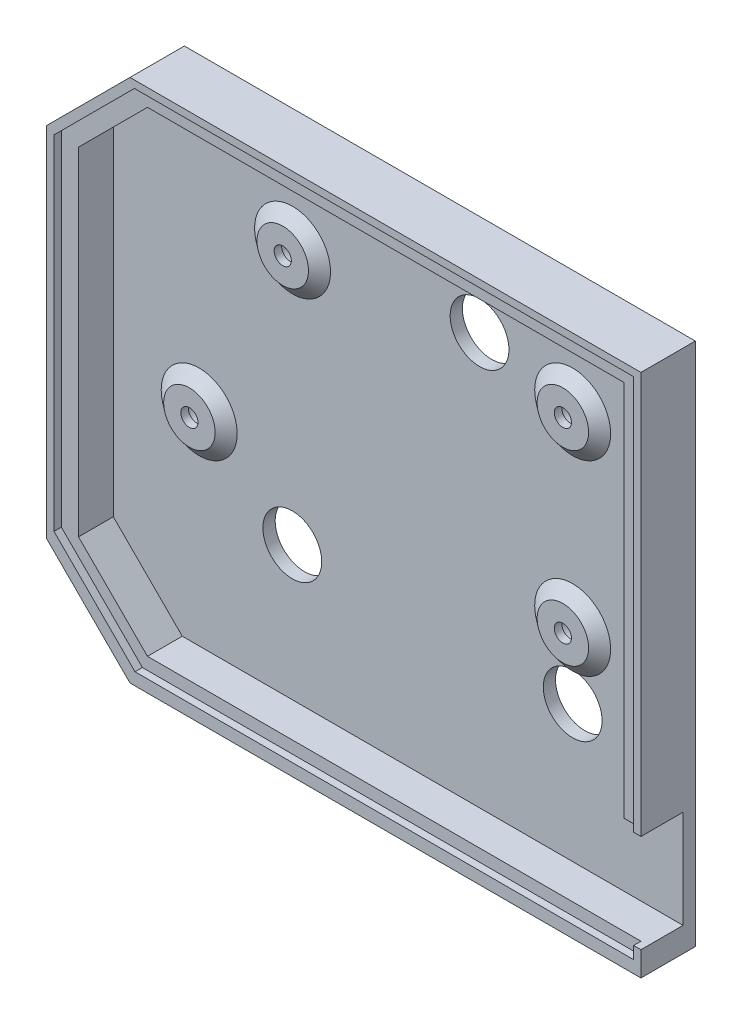
SolidWorks part; units mm, degrees
ref_plane "Plan de face" through (0, 0, 0) normal (0, 0, 1) x (1, 0, 0)
ref_plane "Plan de dessus" through (0, 0, 0) normal (0, 1, 0) x (1, 0, 0)
ref_plane "Plan de droite" through (0, 0, 0) normal (1, 0, 0) x (0, 0, -1)
sketch "Esquisse1" plane through (0, 0, 0) normal (0, 0, 1) x (1, 0, 0)
  line L0 (0, -85) -> (17, -102)
  line L4 (121.25, 5) -> (121.25, -102)
  line L5 (17, 5) -> (0, -12)
  line L7 (121.25, 5) -> (17, 5)
  line L8 (0, -12) -> (0, -85)
  line L9 (17, -102) -> (121.25, -102)
  dimension "D1" = 107
  dimension "D2" = 121.25
  dimension "D3" = 17
  dimension "D4" = 17
  dimension "D5" = 17
  dimension "D6" = 17
extrude "Boss.-Extru.1" add sketch "Esquisse1" along normal blind 2.5
sketch "Esquisse2" plane through (0, 0, 2.5) normal (0, 0, 1) x (1, 0, 0)
  line L0 (0, -12) -> (0, -85) construction
  line L1 (5, 0) -> (116.25, 0) construction
  line L2 (5, 0) -> (5, -97) construction
  line L3 (5, -97) -> (116.25, -97) construction
  line L4 (116.25, 0) -> (116.25, -97) construction
  line L5 (17, -102) -> (121.25, -102) construction
  line L6 (121.25, -102) -> (121.25, 5) construction
  line L7 (121.25, 5) -> (17, 5) construction
  line L9 (5, -82.9289) -> (19.0711, -97)
  line L10 (0, -85) -> (17, -102) construction
  line L11 (5, -14.0711) -> (19.0711, 0)
  line L12 (17, 5) -> (0, -12) construction
  line L13 (116.25, 0) -> (19.0711, 0)
  line L14 (5, -14.0711) -> (5, -82.9289)
  line L15 (19.0711, -97) -> (116.25, -97)
  line L16 (121.25, 5) -> (121.25, -102) construction
  line L17 (121.25, -102) -> (17, -102)
  line L18 (17, -102) -> (0, -85)
  line L19 (0, -85) -> (0, -12)
  line L20 (0, -12) -> (17, 5)
  line L21 (17, 5) -> (121.25, 5)
  line L30 (121.25, -2.5) -> (121.25, 5)
  line L31 (116.25, -97) -> (121.25, -97)
  line L32 (121.25, -97) -> (121.25, -102)
  line L33 (116.25, 0) -> (116.25, -77)
  line L34 (116.25, -77) -> (121.25, -77)
  line L35 (121.25, -77) -> (121.25, -2.5)
  point P24 (118.75, -97)
  dimension "D1" = 5
  dimension "D2" = 5
  dimension "D3" = 5
  dimension "D4" = 5
  dimension "D5" = 5
  dimension "D6" = 5
  dimension "D7" = 20
extrude "Boss.-Extru.2" add sketch "Esquisse2" along normal blind 8.6
sketch "Esquisse4" plane through (0, 0, 2.5) normal (0, 0, 1) x (1, 0, 0)
  line L0 (116.25, 0) -> (116.25, -77) construction
  line L1 (19.0711, 0) -> (116.25, 0) construction
  point P0 (41.57, -17.53)
  point P1 (22.52, -55.63)
  point P2 (98.72, -55.63)
  point P3 (98.72, -17.53)
  dimension "D1" = 17.53
  dimension "D2" = 17.53
  dimension "D3" = 38.1
  dimension "D4" = 57.15
  dimension "D5" = 76.2
ref_axis "Axe1" through (98.72, -55.63, 2.5) along (0, 0, 1)
ref_axis "Axe2" through (22.52, -55.63, 2.5) along (0, 0, 1)
ref_axis "Axe3" through (41.57, -17.53, 2.5) along (0, 0, 1)
ref_axis "Axe4" through (98.72, -17.53, 2.5) along (0, 0, 1)
ref_plane "Plan1" through (0, -55.63, 0) normal (0, -1, 0) x (-1, 0, 0)
ref_plane "Plan2" through (0, -17.53, 0) normal (0, 1, 0) x (1, 0, 0)
sketch "Esquisse9" plane through (0, -55.63, 0) normal (0, -1, 0) x (-1, 0, 0)
  line L0 (-96.97, -2.5) -> (-90.97, -2.5)
  line L1 (-90.97, -2.5) -> (-93.47, -4.5)
  line L2 (-93.47, -4.5) -> (-96.97, -4.5)
  line L3 (-96.97, -4.5) -> (-96.97, -2.5)
  line L4 (-98.72, -2.5) -> (-98.72, -52.4632) construction
  point P0 (-98.5795, 0)
  dimension "D1" = 2
  dimension "D2" = 1.75
  dimension "D3" = 3.5
  dimension "D4" = 6
ref_point "Point1"
ref_point "Point2"
ref_point "Point3"
ref_point "Point4"
revolve "Révolution1" add sketch "Esquisse9" angle 360 about axis through (98.72, -55.63, 2.5) along (0, 0, 1)
sketch "Esquisse11" plane through (0, -55.63, 0) normal (0, -1, 0) x (-1, 0, 0)
  line L0 (-24.27, -2.5) -> (-30.27, -2.5)
  line L1 (-30.27, -2.5) -> (-27.77, -4.5)
  line L2 (-27.77, -4.5) -> (-24.27, -4.5)
  line L3 (-24.27, -4.5) -> (-24.27, -2.5)
  line L4 (-22.52, -2.5) -> (-22.52, -52.4632) construction
  dimension "D1" = 1.75
  dimension "D2" = 3.5
  dimension "D3" = 6
  dimension "D4" = 2
revolve "Révolution2" add sketch "Esquisse11" angle 360 about axis through (22.52, -55.63, 2.5) along (0, 0, 1)
sketch "Esquisse12" plane through (0, -17.53, 0) normal (0, 1, 0) x (1, 0, 0)
  line L0 (96.97, -2.5) -> (90.97, -2.5)
  line L1 (90.97, -2.5) -> (93.47, -4.5)
  line L2 (93.47, -4.5) -> (96.97, -4.5)
  line L3 (96.97, -4.5) -> (96.97, -2.5)
  line L4 (98.72, -2.5) -> (98.72, -52.4632) construction
  dimension "D1" = 1.75
  dimension "D2" = 2
  dimension "D3" = 3.5
  dimension "D4" = 6
revolve "Révolution3" add sketch "Esquisse12" angle 360 about axis through (98.72, -17.53, 2.5) along (0, 0, 1)
sketch "Esquisse13" plane through (0, -17.53, 0) normal (0, 1, 0) x (1, 0, 0)
  line L0 (43.32, -2.5) -> (49.32, -2.5)
  line L1 (49.32, -2.5) -> (46.82, -4.5)
  line L2 (46.82, -4.5) -> (43.32, -4.5)
  line L3 (43.32, -4.5) -> (43.32, -2.5)
  line L4 (41.57, -2.5) -> (41.57, -52.4632) construction
  dimension "D1" = 1.75
  dimension "D2" = 3.5
  dimension "D3" = 6
  dimension "D4" = 2
revolve "Révolution4" add sketch "Esquisse13" angle 360 about axis through (41.57, -17.53, 2.5) along (0, 0, 1)
hole_wizard "Dégagement M31" positions "Esquisse14" profile "Esquisse15" hole size "M3" standard "Ansi Metric" end condition up to next
sketch "Esquisse14" plane through (0, 0, 2.5) normal (0, 0, 1) x (1, 0, 0)
  point P0 (98.72, -55.63)
  point P3 (22.52, -55.63)
  point P6 (98.72, -17.53)
  point P9 (41.57, -17.53)
sketch "Esquisse15" plane through (98.72, -55.63, 2.5) normal (1, 0, 0) x (0, -1, 0)
  line L0 (0, 0) -> (0, 2.5)
  line L1 (0, 2.5) -> (1.8, 2.5)
  line L2 (1.8, 2.5) -> (1.8, 0)
  line L5 (1.8, 0) -> (0, 0)
  line L11 (0, -6.35) -> (0, 107.95) construction
  dimension "Diamètre du perçage jusqu'au prochain" = 3.6
  dimension "Profondeur du perçage jusqu'au prochain" = 2.5
ref_point "Point5"
ref_point "Point6"
ref_point "Point7"
ref_point "Point8"
sketch "Esquisse16" plane through (0, 0, 0) normal (0, 0, -1) x (-1, 0, 0)
  circle A0 centre (-22.52, -55.63) radius 2.7
  circle A1 centre (-98.72, -55.63) radius 2.7
  circle A2 centre (-98.72, -17.53) radius 2.7
  circle A3 centre (-41.57, -17.53) radius 2.7
  dimension "D1" = 5.4
  dimension "D2" = 5.4
  dimension "D3" = 5.4
  dimension "D4" = 5.4
extrude "Enlèv. mat.-Extru.2" cut sketch "Esquisse16" against normal blind 3
sketch "Esquisse17" plane through (0, 0, 11.1) normal (0, 0, 1) x (1, 0, 0)
  line L0 (17, -102) -> (121.25, -102) construction
  line L1 (119.75, -99.5) -> (1.5, -99.5) construction
  line L2 (119.75, -99.5) -> (119.75, 3.5)
  line L3 (119.75, 3.5) -> (1.5, 3.5) construction
  line L4 (1.5, -99.5) -> (1.5, 3.5) construction
  line L5 (121.25, -102) -> (121.25, -97) construction
  line L6 (0, -12) -> (0, -85) construction
  line L7 (121.25, 5) -> (17, 5) construction
  line L8 (-697.163, -711.5671) -> (34658.1761, 34643.7719) construction
  line L9 (17, 5) -> (0, -12) construction
  line L10 (119.75, 3.5) -> (17.9042, 3.5)
  line L11 (17.9042, 3.5) -> (1.5, -12.9042)
  line L12 (119.75, 3.5) -> (116.25, 0) construction
  line L18 (15.5687, -97.0332) -> (-9.8376, -71.6268) construction
  line L19 (0, -85) -> (17, -102) construction
  line L20 (119.75, -99.5) -> (18.0355, -99.5)
  line L21 (18.0355, -99.5) -> (1.5, -82.9645)
  line L24 (1.5, -12.9042) -> (1.5, -82.9645)
  dimension "D1" = 2.5
  dimension "D2" = 1.5
  dimension "D3" = 1.5
  dimension "D4" = 1.5
  dimension "D5" = 2.5
  dimension "D6" = 1.7
extrude "Enlèv. mat.-Extru.3" cut sketch "Esquisse17" against normal blind 1.5
sketch "Esquisse20" plane through (0, 0, 2.5) normal (0, 0, 1) x (1, 0, 0)
  circle A0 centre (98.72, -69.13) radius 6
  circle A1 centre (41.52, -69.63) radius 6
  circle A2 centre (79.72, -13.03) radius 6
  dimension "D1" = 13.5
  dimension "D3" = 19
  dimension "D5" = 19
  dimension "D2" = 0
  dimension "D4" = 14
  dimension "D6" = 4.5
extrude "Enlèv. mat.-Extru.4" cut sketch "Esquisse20" against normal blind 10 and the other way blind 10
chamfer "Chanfrein3" distance 1 angle 30 4 edges at (38.87, -17.53, 3) (96.02, -17.53, 3) (96.02, -55.63, 3) (19.82, -55.63, 3) first distance on face at (38.87, -17.53, 3) first distance on face at (96.97, -17.53, 3) first distance on face at (96.02, -55.63, 3) first distance on face at (20.77, -55.63, 3)
equation "\"r_ext\"= 5.4"
equation "\"D1@Esquisse16\"=\"r_ext\""
equation "\"D2@Esquisse16\"=\"r_ext\""
equation "\"D3@Esquisse16\"=\"r_ext\""
equation "\"D4@Esquisse16\"=\"r_ext\""
